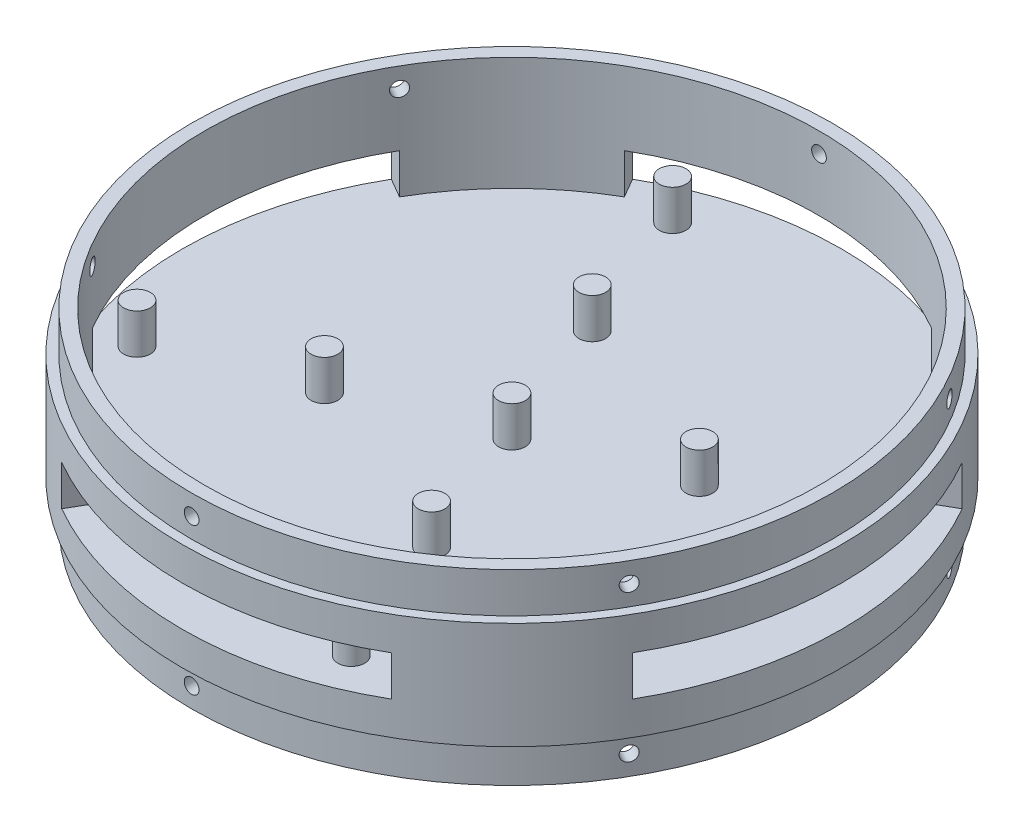
SolidWorks part; units mm, degrees
ref_plane "Front Plane" through (0, 0, 0) normal (0, 0, 1) x (1, 0, 0)
ref_plane "Top Plane" through (0, 0, 0) normal (0, 1, 0) x (1, 0, 0)
ref_plane "Right Plane" through (0, 0, 0) normal (1, 0, 0) x (0, 0, -1)
sketch "Sketch1" plane through (0, 0, 0) normal (0, 1, 0) x (1, 0, 0)
  line L0 (0, 0) -> (-39.1795, 67.8609)
  line L1 (0, 0) -> (39.1795, 67.8609)
  line L2 (0, 0) -> (0, 72.1431) construction
  circle A0 centre (0, 0) radius 78.359
  circle A1 centre (0, 0) radius 73.025
  circle A2 centre (0, 0) radius 76.1746
  dimension "D1" = 156.718
  dimension "D2" = 146.05
  dimension "D3" = 152.3492
  dimension "D4" = 60
extrude "Boss-Extrude1" add sketch "Sketch1" along normal blind 25.4 contours L2 A2 L1 A0 | L2 A1 L1 A2 | L2 A2 L1 A1 | L2 A0 L1 A2 | A2 L2 A1 L0 | A0 L2 A2 L0 | A2 L2 A0 L0 | A1 L2 A2 L0 region at (-37.5543, 0, 65.046) region at (-36.6308, 0, -64.9916) region at (-39.159, 0, 67.8254) region at (-37.9464, 0, -67.3117)
ref_plane "Plane1" through (0, 12.7, 0) normal (0, 1, 0) x (1, 0, 0)
extrude "Boss-Extrude2" add sketch "Sketch1<3>" along normal blind 9.525 from surface contours A2 L2 A1 L0 | L2 A2 L1 A1 | L2 A1 L1 A2 | A1 L2 A2 L0 region at (-37.5543, 0, 65.046) region at (-36.6308, 0, -64.9916) starting at face at (0, 25.4, 73.025)
sketch "Sketch1<3>" plane through (0, 0, 0) normal (0, 1, 0) x (1, 0, 0) same geometry as "Sketch1"
extrude "Boss-Extrude3" add sketch "Sketch1<4>" against normal blind 9.525 contours A2 L2 A1 L0 | A1 L2 A2 L0 | L2 A1 L1 A2 | L2 A2 L1 A1 region at (-37.5543, 0, 65.046) region at (-36.6308, 0, -64.9916)
sketch "Sketch1<4>" plane through (0, 0, 0) normal (0, 1, 0) x (1, 0, 0) same geometry as "Sketch1"
ref_plane "Plane2" through (0, 0, -76.1746) normal (0, 0, -1) x (-1, 0, 0)
ref_axis "Axis1" through (0, 0, 0) along (0, 1, 0)
sketch "Sketch3" plane through (0, 0, -76.1746) normal (0, 0, -1) x (-1, 0, 0)
  line L0 (76.1746, 0) -> (-76.1746, 0) construction
  line L1 (-76.1746, -9.525) -> (76.1746, -9.525) construction
  line L2 (76.1746, 25.4) -> (-76.1746, 25.4) construction
  line L3 (76.1746, 34.925) -> (-76.1746, 34.925) construction
  line L4 (76.1746, 0) -> (-76.1746, 0)
  line L5 (-76.1746, -9.525) -> (76.1746, -9.525)
  line L6 (76.1746, 25.4) -> (-76.1746, 25.4)
  line L7 (76.1746, 34.925) -> (-76.1746, 34.925)
  line L8 (0, 34.925) -> (0, 25.4)
  line L9 (0, 0) -> (0, -9.525)
  circle A0 centre (0, 30.1625) radius 1.75
  circle A1 centre (0, -4.7625) radius 1.75
  point P12 (0, 30.1625)
  point P13 (0, -4.7625)
  point P14 (-77.5445, 179.1871)
  dimension "D1" = 3.5
extrude "Cut-Extrude2" cut sketch "Sketch3" against normal up to next contours L8 A0 | L8 A0 | L9 A1 | L9 A1 region at (-0.7427, 30.1625, -76.1746) region at (0.7427, 30.1625, -76.1746) region at (-0.7427, -4.7625, -76.1746) region at (0.7427, -4.7625, -76.1746)
extrude "Cut-Extrude3" cut sketch "Sketch1<7>" against normal mid plane 9.525 from surface contours L2 A1 L1 A2 | A1 L2 A2 L0 | A2 L2 A0 L0 | L2 A2 L1 A0 region at (-36.6308, 0, -64.9916) region at (-37.9464, 0, -67.3117) starting at plane "Plane1"
sketch "Sketch1<7>" plane through (0, 0, 0) normal (0, 1, 0) x (1, 0, 0) same geometry as "Sketch1"
pattern_circular "CirPattern2" count 4 over 360 about axis through (0, 0, 0) along (0, 1, 0) of "Cut-Extrude3"
pattern_circular "CirPattern3" count 6 over 360 about axis through (0, 0, 0) along (0, 1, 0) of "Cut-Extrude2"
ref_plane "Plane3" through (0, 7.9375, 0) normal (0, 1, 0) x (1, 0, 0)
sketch "Sketch4" plane through (0, 7.9375, 0) normal (0, 1, 0) x (1, 0, 0)
  circle A0 centre (0, 0) radius 73.025
extrude "Boss-Extrude4" add sketch "Sketch4" against normal blind 6.35
sketch "Sketch5" plane through (0, 7.9375, 0) normal (0, 1, 0) x (1, 0, 0)
  line L0 (-39.1795, 67.8609) -> (-36.5125, 63.2415) construction
  line L1 (-25.4707, 63.6746) -> (0, 0) construction
  circle A0 centre (-25.4707, 63.6746) radius 3.175
  circle A2 centre (0, 0) radius 3.175
  circle A3 centre (-12.7354, 31.8373) radius 3.175
  dimension "D1" = 6.35
  dimension "D4" = 6.35
  dimension "D5" = 6.35
  dimension "D2" = 68.58
  dimension "D3" = 9.779
  dimension "D6" = 34.29
extrude "Boss-Extrude5" add sketch "Sketch5" along normal blind 9.525
pattern_circular "CirPattern4" count 4 over 360 about axis through (0, 7.9375, 0) along (0, 1, 0) of "Boss-Extrude5"
equation "\"AB_Coupler_OD_Length\"= 1in"
equation "\"AB_Coupling_Section_Length\"= 0.375in"
equation "\"AB_Coupler_Length\"= \"AB_Coupler_OD_Length\" + \"AB_Coupling_Section_Length\" * 2"
equation "\"D1@Boss-Extrude2\"=\"AB_Coupling_Section_Length\""
equation "\"D1@Boss-Extrude3\"=\"AB_Coupling_Section_Length\""
equation "\"D1@Boss-Extrude1\" = \"AB_Coupler_OD_Length\""
equation "\"Cutout_Angle\" = 60"
equation "\"AB_Coupler_Num_Screws\"= 6"
equation "\"Num_Cutouts\" = 4"
equation "\"D4@Sketch1\"=\"Cutout_Angle\""
equation "\"D1@CirPattern2\"=\"Num_Cutouts\""
equation "\"D1@CirPattern3\"=\"AB_Coupler_Num_Screws\""
equation "\"AB_Coupler_OD\"= 6.17in"
equation "\"AB_Coupler_ID\"= 5.75in"
equation "\"AB_Coupler_Surface_Diameter\"= 5.998in"
equation "\"D3@Sketch1\"=\"AB_Coupler_Surface_Diameter\""
equation "\"D2@Sketch1\"=\"AB_Coupler_ID\""
equation "\"D1@Sketch1\"=\"AB_Coupler_OD\""
equation "\"AB_Coupling_Screw_Diameter\"= 0.1065in"
equation "\"Aft_Section_Length\"= 40in"
equation "\"Aft_Lower_Length\"= 20in"
equation "\"Aft_Upper_Length\"= \"Aft_Section_Length\" - \"Aft_Lower_Length\" - \"AB_Coupler_OD_Length\""
equation "\"Mid_Coupler_Length\" = 10in"
equation "\"Lead_Screw_Dist\" = 2.25in"
equation "\"Lead_Screw_Diam\" = (27/64)*1in"
equation "\"Lead_Screw_Length\" = (\"Mid_Coupler_Length\" + 2*0.375in + 2*0.5in)"
equation "\"Bodytube_OD\" = 6.17in"
equation "\"D2@Sketch5\"=2.7in"
equation "\"Paddle_Pin_Offset\" = \"Bodytube_OD\"/2-\"Paddle_Pin_Radius\""
equation "\"D3@Sketch5\"=\"Paddle_Pin_Offset\""
equation "\"D1@CirPattern4\"=\"Num_Cutouts\""
equation "\"Bodytube_ID\" = 5.998in"
equation "\"Paddle_Pin_Radius\" = 2.7in"
